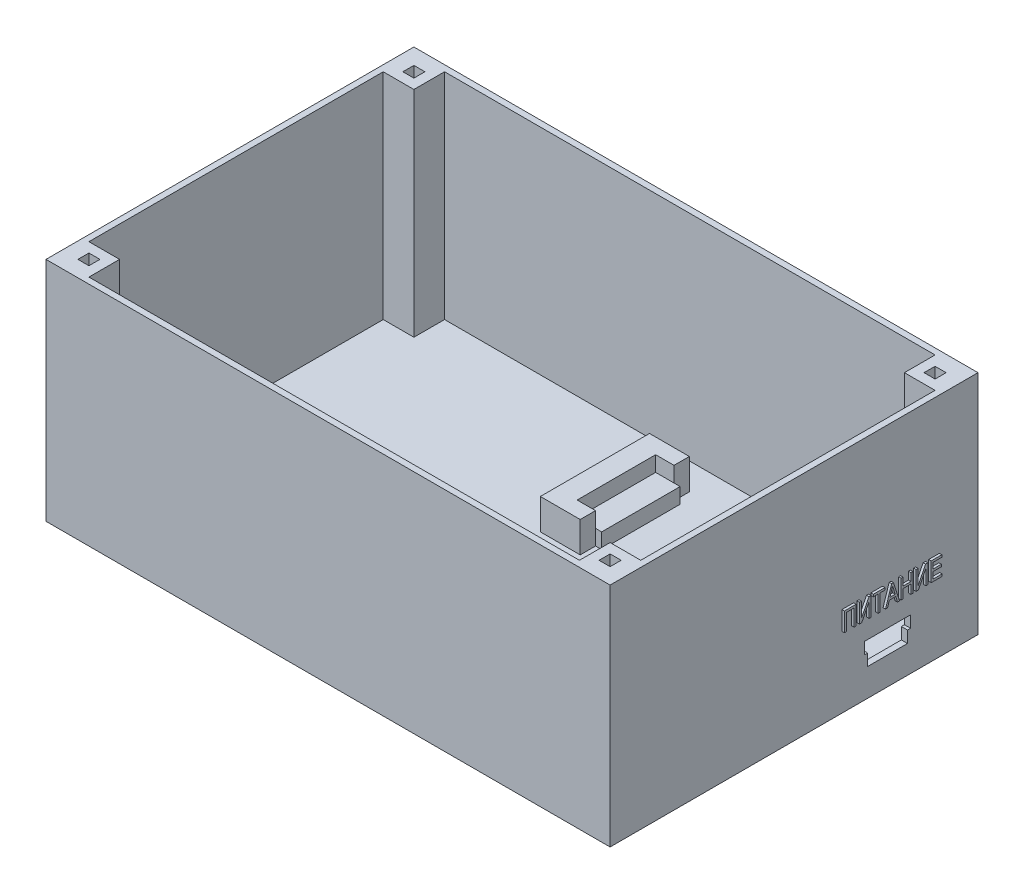
SolidWorks part; units mm, degrees
ref_plane "Спереди" through (0, 0, 0) normal (0, 0, 1) x (1, 0, 0)
ref_plane "Сверху" through (0, 0, 0) normal (0, 1, 0) x (1, 0, 0)
ref_plane "Справа" through (0, 0, 0) normal (1, 0, 0) x (0, 0, -1)
sketch "Эскиз2" plane through (0, 0, 0) normal (0, 1, 0) x (1, 0, 0)
  line L1 (0, 0) -> (92, 0)
  line L2 (0, 0) -> (0, 60)
  line L3 (0, 60) -> (92, 60)
  line L4 (92, 0) -> (92, 60)
extrude "Бобышка-Вытянуть1" add sketch "Эскиз2" along normal blind 2
sketch "Эскиз14" plane through (0, 2, 0) normal (0, 1, 0) x (1, 0, 0)
  line L0 (0, 60) -> (0, 0) construction
  line L1 (1, 59) -> (91, 59)
  line L2 (1, 59) -> (1, 1)
  line L3 (1, 1) -> (91, 1)
  line L4 (91, 59) -> (91, 1)
  line L5 (92, 60) -> (0, 60) construction
  line L6 (0, 0) -> (92, 0) construction
  line L7 (92, 0) -> (92, 60) construction
  line L9 (92, 0) -> (0, 0)
  line L10 (92, 0) -> (92, 60)
  line L11 (92, 60) -> (0, 60)
  line L12 (0, 0) -> (0, 60)
  dimension "D1" = 1
  dimension "D2" = 1
  dimension "D3" = 1
  dimension "D4" = 1
extrude "Бобышка-Вытянуть9" add sketch "Эскиз14" along normal blind 35 separate body
sketch "Эскиз16" plane through (0, 2, 0) normal (0, 1, 0) x (1, 0, 0)
  line L0 (1, 56.5) -> (6, 56.5) construction
  line L1 (6, 54) -> (1, 54)
  line L2 (6, 54) -> (6, 59)
  line L3 (6, 59) -> (1, 59)
  line L4 (1, 54) -> (1, 59)
  line L5 (3.5, 54) -> (3.5, 59) construction
  line L6 (86, 3.5) -> (91, 3.5) construction
  line L11 (91, 1) -> (86, 1)
  line L12 (91, 1) -> (91, 6)
  line L17 (91, 6) -> (86, 6)
  line L18 (86, 1) -> (86, 6)
  line L23 (88.5, 1) -> (88.5, 6) construction
  line L24 (1, 3.5) -> (6, 3.5) construction
  line L25 (6, 1) -> (1, 1)
  line L26 (6, 1) -> (6, 6)
  line L27 (6, 6) -> (1, 6)
  line L28 (1, 1) -> (1, 6)
  line L29 (3.5, 1) -> (3.5, 6) construction
  line L30 (86, 56.5) -> (91, 56.5) construction
  line L31 (91, 54) -> (86, 54)
  line L32 (91, 54) -> (91, 59)
  line L33 (91, 59) -> (86, 59)
  line L34 (86, 54) -> (86, 59)
  line L35 (88.5, 54) -> (88.5, 59) construction
  line L36 (88.5, 57.4) -> (88.5, 55.6) construction
  line L37 (87.6, 57.4) -> (89.4, 57.4)
  line L38 (87.6, 57.4) -> (87.6, 55.6)
  line L39 (87.6, 55.6) -> (89.4, 55.6)
  line L40 (89.4, 57.4) -> (89.4, 55.6)
  line L41 (87.6, 56.5) -> (89.4, 56.5) construction
  line L42 (3.5, 57.4) -> (3.5, 55.6) construction
  line L47 (2.6, 57.4) -> (4.4, 57.4)
  line L48 (2.6, 57.4) -> (2.6, 55.6)
  line L53 (2.6, 55.6) -> (4.4, 55.6)
  line L54 (4.4, 57.4) -> (4.4, 55.6)
  line L59 (2.6, 56.5) -> (4.4, 56.5) construction
  line L60 (3.5, 4.4) -> (3.5, 2.6) construction
  line L61 (2.6, 4.4) -> (4.4, 4.4)
  line L62 (2.6, 4.4) -> (2.6, 2.6)
  line L63 (2.6, 2.6) -> (4.4, 2.6)
  line L64 (4.4, 4.4) -> (4.4, 2.6)
  line L65 (2.6, 3.5) -> (4.4, 3.5) construction
  line L66 (88.5, 4.4) -> (88.5, 2.6) construction
  line L67 (87.6, 4.4) -> (89.4, 4.4)
  line L68 (87.6, 4.4) -> (87.6, 2.6)
  line L69 (87.6, 2.6) -> (89.4, 2.6)
  line L70 (89.4, 4.4) -> (89.4, 2.6)
  line L71 (87.6, 3.5) -> (89.4, 3.5) construction
  dimension "D2" = 5
  dimension "D3" = 5
  dimension "D5" = 5
  dimension "D6" = 5
  dimension "D8" = 5
  dimension "D9" = 5
  dimension "D11" = 5
  dimension "D12" = 5
sketch "Эскиз17" plane through (92, 0, 0) normal (1, 0, 0) x (0, 0, -1)
  line L0 (41.5, 8.3) -> (49, 8.3)
  line L1 (49, 8.3) -> (49, 6.4)
  line L2 (49, 6.4) -> (48.5, 6.4)
  line L3 (48.5, 6.4) -> (48.5, 4.5)
  line L4 (48.5, 4.5) -> (42, 4.5)
  line L5 (42, 4.5) -> (42, 6.4)
  line L6 (42, 6.4) -> (41.5, 6.4)
  line L7 (41.5, 6.4) -> (41.5, 8.3)
  line L8 (0, 2) -> (60, 2) construction
  line L9 (59, 37) -> (59, 2) construction
  dimension "D1" = 7.5
  dimension "D2" = 6.5
  dimension "D3" = 3.8
  dimension "D4" = 1.9
  dimension "D5" = 2.5
  dimension "D6" = 10
sketch "Эскиз18" plane through (0, 2, 0) normal (0, 1, 0) x (1, 0, 0)
  line L0 (91, 1) -> (91, 59) construction
  line L1 (47.3, 52.1241) -> (51.3, 52.1241)
  line L2 (47.3, 52.1241) -> (47.3, 39.3241)
  line L3 (47.3, 39.3241) -> (51.3, 39.3241)
  line L4 (51.3, 52.1241) -> (51.3, 39.3241)
  dimension "D1" = 12.8
  dimension "D2" = 4
  dimension "D3" = 43.7
extrude "Бобышка-Вытянуть12" add sketch "Эскиз18" along normal blind 2.5
sketch "Эскиз19" plane through (0, 2, 0) normal (0, 1, 0) x (1, 0, 0)
  line L1 (47.3, 39.3241) -> (50.3, 39.3241)
  line L2 (47.3, 39.3241) -> (47.3, 36.8241)
  line L3 (47.3, 36.8241) -> (50.3, 36.8241)
  line L4 (50.3, 39.3241) -> (50.3, 36.8241)
  line L5 (47.3, 52.1241) -> (50.3, 52.1241)
  line L6 (47.3, 52.1241) -> (47.3, 54.6241)
  line L7 (47.3, 54.6241) -> (50.3, 54.6241)
  line L8 (50.3, 52.1241) -> (50.3, 54.6241)
extrude "Бобышка-Вытянуть13" add sketch "Эскиз19" along normal blind 5
sketch "Эскиз20" plane through (0, 2, 0) normal (0, 1, 0) x (1, 0, 0)
  line L0 (47.3, 54.6241) -> (47.3, 36.8241) construction
  line L1 (47.3, 54.6241) -> (43.8, 54.6241)
  line L2 (47.3, 54.6241) -> (47.3, 36.8241)
  line L3 (47.3, 36.8241) -> (43.8, 36.8241)
  line L4 (43.8, 54.6241) -> (43.8, 36.8241)
extrude "Бобышка-Вытянуть14" add sketch "Эскиз20" along normal blind 5
extrude "Вырез-Вытянуть1" cut sketch "Эскиз17" against normal blind 5 contours L0 L1 L2 L3 L4 L5 L6 L7
sketch "Эскиз21" plane through (0, 2, 0) normal (0, 1, 0) x (1, 0, 0)
  line L0 (1, 6) -> (3.7061, 6)
  line L1 (88.2939, 6) -> (91, 6)
  line L2 (88.2939, 6) -> (88.2939, 26.3)
  line L3 (88.2939, 26.3) -> (91, 26.3)
  line L4 (91, 6) -> (91, 26.3)
  line L5 (1, 6) -> (1, 26.3)
  line L6 (1, 26.3) -> (3.7061, 26.3)
  line L7 (3.7061, 6) -> (3.7061, 26.3)
  line L9 (1, 59) -> (1, 1) construction
  line L11 (6, 6) -> (1, 6) construction
  dimension "D1" = 20.3
  dimension "D2" = 90
extrude "Бобышка-Вытянуть16" add sketch "Эскиз21" along normal blind 2.5
sketch "Эскиз22" plane through (0, 2, 0) normal (0, 1, 0) x (1, 0, 0)
  line L0 (1, 59) -> (1, 26.3) construction
  line L1 (3.7061, 26.3) -> (1, 26.3)
  line L2 (3.7061, 26.3) -> (3.7061, 28.8)
  line L3 (3.7061, 28.8) -> (1, 28.8)
  line L4 (1, 26.3) -> (1, 28.8)
  line L6 (91, 26.3) -> (88.2939, 26.3)
  line L7 (91, 26.3) -> (91, 28.8)
  line L8 (91, 28.8) -> (88.2939, 28.8)
  line L9 (88.2939, 26.3) -> (88.2939, 28.8)
extrude "Бобышка-Вытянуть17" add sketch "Эскиз22" along normal blind 5
extrude "Бобышка-Вытянуть19" add sketch "Эскиз16" along normal blind 35
sketch "Эскиз23" plane through (92, 0, 0) normal (1, 0, 0) x (0, 0, -1)
  text T0 "ПИТАНИЕ" font "Arial" height in points 12
extrude "Бобышка-Вытянуть20" add sketch "Эскиз23" along normal blind 0.4
sketch "Эскиз24" plane through (1, 0, 0) normal (1, 0, 0) x (0, 0, -1)
  line L0 (26.3, 4.5) -> (6, 4.5) construction
  line L1 (12.8962, 14.1) -> (22.5962, 14.1)
  line L2 (12.8962, 14.1) -> (12.8962, 9.5)
  line L3 (12.8962, 9.5) -> (22.5962, 9.5)
  line L4 (22.5962, 14.1) -> (22.5962, 9.5)
  point P4 (0, 0)
  dimension "D1" = 9.7
  dimension "D2" = 4.6
  dimension "D3" = 5
extrude "Вырез-Вытянуть2" cut sketch "Эскиз24" against normal blind 1 contours L2 L1 L4 L3
sketch "Эскиз25" plane through (0, 0, 0) normal (-1, 0, 0) x (0, 0, 1)
  text T0 "UART"
extrude "Бобышка-Вытянуть21" add sketch "Эскиз25" along normal blind 0.4
